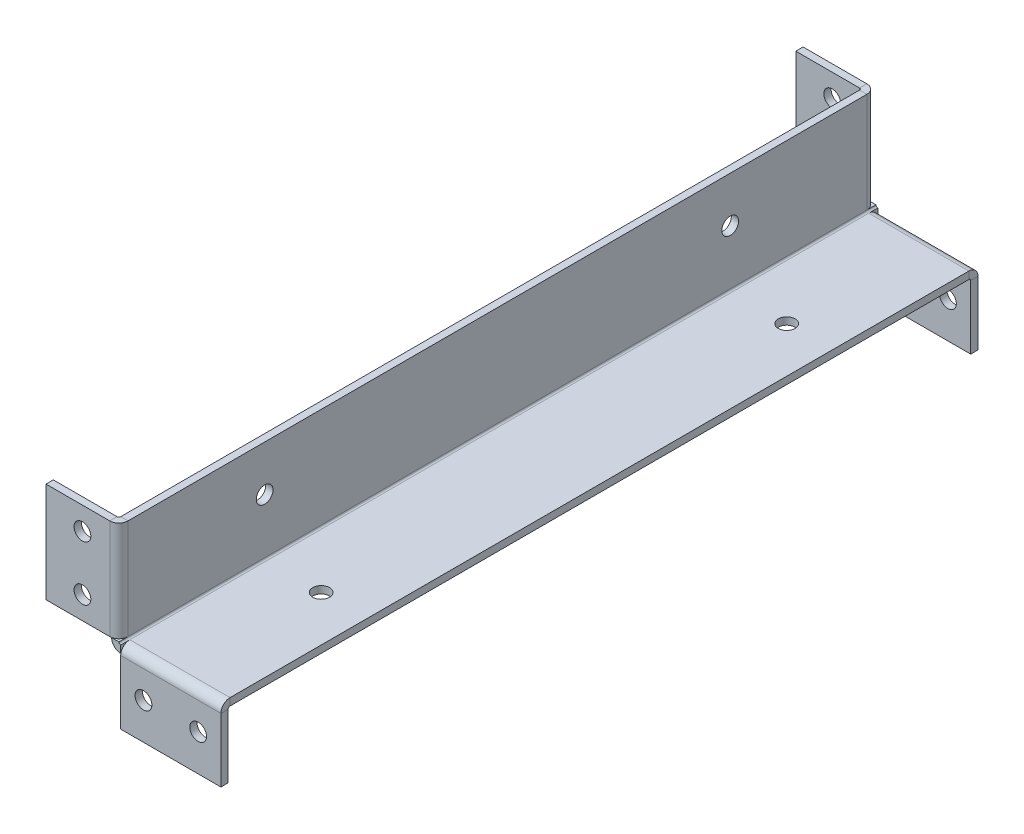
SolidWorks part; units mm, degrees
note: The reader was unsure of these and kept them because the rebuilt part matched: flange length of "Edge-Flange1", "Edge-Flange2".
ref_plane "Front Plane" through (0, 0, 0) normal (0, 0, 1) x (1, 0, 0)
ref_plane "Top Plane" through (0, 0, 0) normal (0, 1, 0) x (1, 0, 0)
ref_plane "Right Plane" through (0, 0, 0) normal (1, 0, 0) x (0, 0, -1)
sketch "Sketch1" plane through (0, 0, 0) normal (0, 1, 0) x (1, 0, 0)
  line L1 (30, 207.75) -> (-30, 207.75)
  line L2 (30, 207.75) -> (30, -207.75)
  line L3 (30, -207.75) -> (-30, -207.75)
  line L4 (-30, 207.75) -> (-30, -207.75)
  line L5 (30, 207.75) -> (-30, -207.75) construction
  line L6 (30, -207.75) -> (-30, 207.75) construction
  point P0 (0, 0)
  dimension "D1" = 60
  dimension "D2" = 415.5
sheet metal parameters "Sheet-Metal1" thickness 4 parameters "D1"=1
base flange "Base-Flange1" sketch "Sketch1" thickness 4 reverse thickness direction yes parameters "D1"=1
edge flange "Edge-Flange1" sketch "Sketch5" flange angle 90 flange length 60 flange position material inside bend radius 1 thickness 4 parameters "D6"=10
sketch "Sketch5" plane through (-30, 4, 0) normal (-1, 0, 0) x (0, 0, 1)
  line L2 (-207.75, 0) -> (-207.75, 56)
  line L3 (-207.75, 56) -> (207.75, 56)
  line L4 (207.75, 56) -> (207.75, 0)
  line L5 (-207.75, 0) -> (207.75, 0) construction
  line L6 (-207.75, 0) -> (207.75, 0)
bend "EdgeBend1" bend radius 1 bend angle 90 parameters "D5"=1
edge flange "Edge-Flange2" sketch "Sketch14" flange profiles "Sketch14", "Sketch15", "Sketch16", "Sketch17" flange angle 90 flange length 40 flange position material inside bend radius 1 thickness 4 relief none parameters "D6"=10, "D8"=0.5
sketch "Sketch14" plane through (-30, 0, 207.75) normal (0, 0, -1) x (0, -1, 0)
  line L1 (-5, 0) -> (-60, 0) construction
  line L2 (-60, 0) -> (-60, 36)
  line L3 (-60, 36) -> (-5, 36)
  line L4 (-5, 36) -> (-5, 0)
  line L5 (-5, 0) -> (-60, 0)
sketch "Sketch15" plane through (0, 0, 207.75) normal (0, 0, -1) x (1, 0, 0)
  line L0 (30, 0) -> (-25, 0) construction
  line L1 (30, 0) -> (-25, 0)
  line L2 (30, 0) -> (30, 36)
  line L3 (30, 36) -> (-25, 36)
  line L4 (-25, 36) -> (-25, 0)
sketch "Sketch16" plane through (-30, 0, -207.75) normal (0, 0, 1) x (0, 1, 0)
  line L0 (60, 0) -> (5, 0) construction
  line L1 (60, 0) -> (5, 0)
  line L2 (60, 0) -> (60, 36)
  line L3 (60, 36) -> (5, 36)
  line L4 (5, 36) -> (5, 0)
sketch "Sketch17" plane through (0, 0, -207.75) normal (0, 0, 1) x (-1, 0, 0)
  line L0 (25, 0) -> (-30, 0) construction
  line L1 (25, 0) -> (-30, 0)
  line L2 (25, 0) -> (25, 36)
  line L3 (25, 36) -> (-30, 36)
  line L4 (-30, 36) -> (-30, 0)
bend "EdgeBend2" bend radius 1 bend angle 90 parameters "D5"=2
bend "EdgeBend3" bend radius 1 bend angle 90 parameters "D5"=3
bend "EdgeBend4" bend radius 1 bend angle 90 parameters "D5"=4
bend "EdgeBend5" bend radius 1 bend angle 90 parameters "D5"=5
sketch "Sketch18" plane through (0, 0, 207.75) normal (0, 0, 1) x (1, 0, 0)
  line L0 (-25, 4) -> (30, 4) construction
  line L1 (-26, 60) -> (-26, 5) construction
  line L2 (-66, 60) -> (-31, 60) construction
  line L3 (30, -1) -> (30, -36) construction
  circle A0 centre (-46, 47.5) radius 4.6
  circle A1 centre (-46, 17.5) radius 4.6
  circle A2 centre (-12.5, -16) radius 4.6
  circle A3 centre (17.5, -16) radius 4.6
  dimension "D7" = 9.2
  dimension "D1" = 30
  dimension "D2" = 30
  dimension "D3" = 20
  dimension "D4" = 20
  dimension "D5" = 12.5
  dimension "D6" = 12.5
extrude "Extrude1" cut sketch "Sketch18" against normal through all normal cut yes
sketch "Sketch19" plane through (-26, 0, 0) normal (1, 0, 0) x (0, 0, -1)
  line L0 (-202.75, 60) -> (202.75, 60) construction
  line L1 (-207.75, 5) -> (-207.75, 60) construction
  line L2 (207.75, 5) -> (207.75, 60) construction
  circle A0 centre (-127.75, 35) radius 4.6
  circle A1 centre (127.75, 35) radius 4.6
  dimension "D4" = 9.2
  dimension "D1" = 25
  dimension "D2" = 80
  dimension "D3" = 80
extrude "Extrude2" cut sketch "Sketch19" against normal blind 4 normal cut yes
sketch "Sketch20" plane through (0, 4, 0) normal (0, 1, 0) x (1, 0, 0)
  line L0 (30, -202.75) -> (30, 202.75) construction
  line L1 (-25, -207.75) -> (30, -207.75) construction
  line L2 (30, 207.75) -> (-25, 207.75) construction
  circle A0 centre (5, 127.75) radius 4.6
  circle A1 centre (5, -127.75) radius 4.6
  dimension "D2" = 9.2
  dimension "D1" = 25
  dimension "D3" = 80
  dimension "D4" = 80
extrude "Extrude3" cut sketch "Sketch20" against normal blind 4 normal cut yes
flat pattern "Flat-Pattern1" [suppressed]
sketch "Bend-Lines1" plane through (0, 4, 0) normal (0, 1, 0) x (-1, 0, 0)
  line L0 (25, -126.4012) -> (-30, -126.4012) construction
  line L1 (82.8023, -126.4012) -> (27.8023, -126.4012) construction
  line L2 (-30, 126.4012) -> (25, 126.4012) construction
  line L3 (27.8023, 126.4012) -> (82.8023, 126.4012) construction
  line L4 (26.4012, -130) -> (26.4012, 130) construction
  line L5 (25, -126.4012) -> (-30, -126.4012) construction
  line L6 (82.8023, -126.4012) -> (27.8023, -126.4012) construction
  line L7 (-30, 126.4012) -> (25, 126.4012) construction
  line L8 (27.8023, 126.4012) -> (82.8023, 126.4012) construction
  line L9 (26.4012, -130) -> (26.4012, 130) construction
bend of the flat pattern "Flatten-<EdgeBend1>1"
bend of the flat pattern "Flatten-<EdgeBend2>1"
bend of the flat pattern "Flatten-<EdgeBend3>1"
bend of the flat pattern "Flatten-<EdgeBend4>1"
bend of the flat pattern "Flatten-<EdgeBend5>1"
